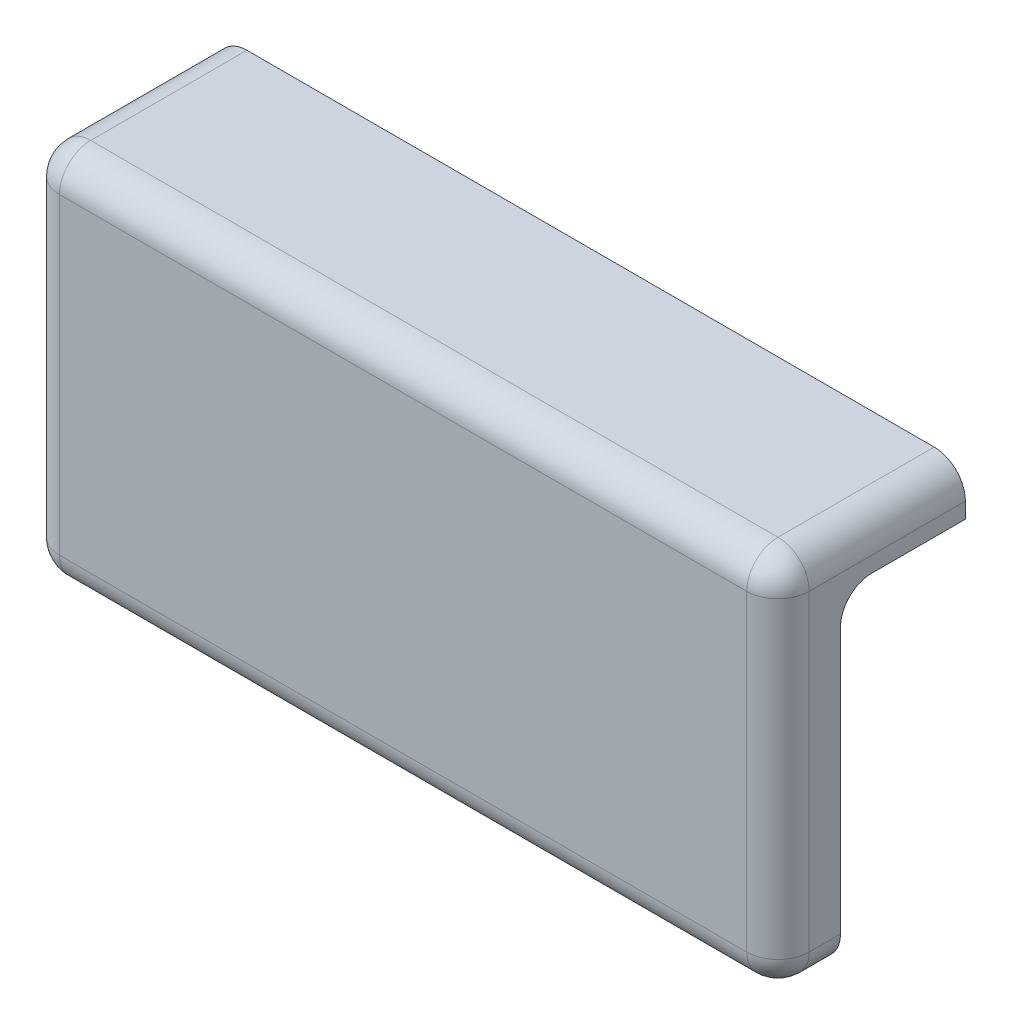
SolidWorks part; units mm, degrees
material "Delrin 2700 NC010, Low Viscosity Acetal Copolymer (SS)"
ref_plane "Front Plane" through (0, 0, 0) normal (0, 0, 1) x (1, 0, 0)
ref_plane "Top Plane" through (0, 0, 0) normal (0, 1, 0) x (1, 0, 0)
ref_plane "Right Plane" through (0, 0, 0) normal (1, 0, 0) x (0, 0, -1)
sketch "Sketch1" plane through (0, 0, 0) normal (1, 0, 0) x (0, 0, -1)
  line L1 (-9.525, -19.05) -> (9.525, -19.05)
  line L2 (-9.525, -19.05) -> (-9.525, 19.05)
  line L3 (-9.525, 19.05) -> (9.525, 19.05)
  line L4 (9.525, -19.05) -> (9.525, 19.05)
  line L5 (-9.525, -19.05) -> (9.525, 19.05) construction
  line L6 (-9.525, 19.05) -> (9.525, -19.05) construction
  point P0 (0, 0)
  dimension "D1" = 38.1
  dimension "D2" = 19.05
extrude "Boss-Extrude1" add sketch "Sketch1" along normal mid plane 76.2
sketch "Sketch2" plane through (0, 0, -9.525) normal (0, 0, -1) x (-1, 0, 0)
  line L0 (-38.1, -19.05) -> (38.1, -19.05) construction
  line L1 (-4.7625, -19.05) -> (4.7625, -19.05)
  line L2 (-4.7625, -19.05) -> (-4.7625, 15.875)
  line L3 (-4.7625, 15.875) -> (4.7625, 15.875)
  line L4 (4.7625, -19.05) -> (4.7625, 15.875)
  point P6 (0, -19.05)
  point P7 (0, -19.05)
  dimension "D1" = 9.525
  dimension "D2" = 34.925
extrude "Cut-Extrude1" cut sketch "Sketch2" against normal offset from surface (12.7 mm away) 6.35 up to face at (0, 0, 9.525)
sketch "Sketch3" plane through (0, 0, -9.525) normal (0, 0, -1) x (-1, 0, 0)
  line L1 (-38.1, -19.05) -> (-9.525, -19.05)
  line L2 (-38.1, -19.05) -> (-38.1, 14.2875)
  line L3 (-38.1, 14.2875) -> (-9.525, 14.2875)
  line L4 (-9.525, -19.05) -> (-9.525, 14.2875)
  line L5 (38.1, -19.05) -> (9.525, -19.05)
  line L6 (38.1, -19.05) -> (38.1, 14.2875)
  line L7 (38.1, 14.2875) -> (9.525, 14.2875)
  line L8 (9.525, -19.05) -> (9.525, 14.2875)
  line L10 (-38.1, 19.05) -> (38.1, 19.05) construction
  dimension "D1" = 19.05
  dimension "D2" = 4.7625
extrude "Cut-Extrude2" cut sketch "Sketch3" against normal up to surface (12.7 mm away) up to face at (0, -1.5875, 3.175)
fillet "Fillet1" radius 3.175 16 edges at (-4.7625, 15.875, -3.175) (4.7625, 15.875, -3.175) (-9.525, 14.2875, -3.175) (9.525, 14.2875, -3.175) (-38.1, 0, 9.525) (0, -19.05, 9.525) (38.1, 0, 9.525) (0, 19.05, 9.525) (38.1, -19.05, 6.35) (-38.1, -19.05, 6.35) (-38.1, 19.05, 0) (38.1, 19.05, 0) (9.525, -2.3813, 3.175) (23.8125, 14.2875, 3.175) (-9.525, -2.3813, 3.175) (-23.8125, 14.2875, 3.175)
hole_wizard "#8 Clearance Hole1" positions "Sketch4" profile "Sketch5" hole size "#8" standard "ANSI Inch" end condition through all
sketch "Sketch4" plane through (9.525, 0, 0) normal (1, 0, 0) x (0, 0, -1)
  line L0 (9.525, -19.05) -> (9.525, 11.1125) construction
  line L1 (0, -19.05) -> (9.525, -19.05) construction
  point P0 (3.175, -12.7)
  point P2 (3.175, 6.35)
  dimension "D1" = 6.35
  dimension "D2" = 6.35
  dimension "D3" = 19.05
sketch "Sketch5" plane through (9.525, -12.7, -3.175) normal (0, 1, 0) x (0, 0, -1)
  line L0 (0, 0) -> (0, 47.625)
  line L1 (0, 47.625) -> (2.2479, 47.625)
  line L2 (2.2479, 47.625) -> (2.2479, 0)
  line L5 (2.2479, 0) -> (0, 0)
  line L11 (0, -6.35) -> (0, 107.95) construction
  dimension "Thru Hole Dia." = 4.4958
  dimension "Thru Hole Depth" = 47.625
fillet "Fillet2" radius 3.175 1 edges at (0, -19.05, 3.175)
